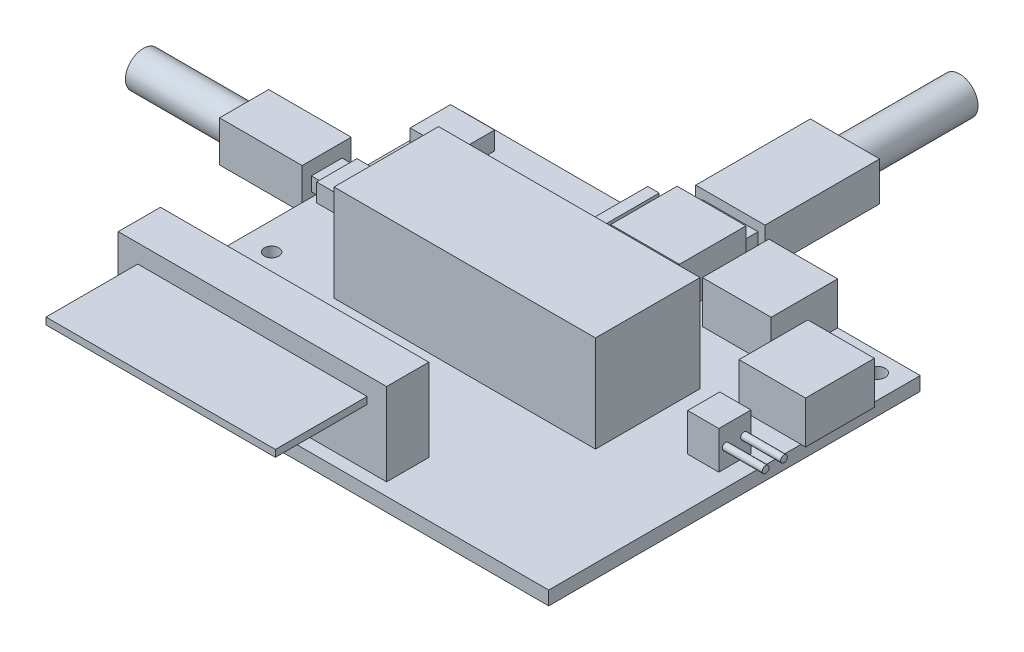
SolidWorks part; units mm, degrees
ref_plane "Front Plane" through (0, 0, 0) normal (0, 0, 1) x (1, 0, 0)
ref_plane "Top Plane" through (0, 0, 0) normal (0, 1, 0) x (1, 0, 0)
ref_plane "Right Plane" through (0, 0, 0) normal (1, 0, 0) x (0, 0, -1)
sketch "Sketch1" plane through (0, 0, 0) normal (0, 1, 0) x (1, 0, 0)
  line L1 (-50, -40.5) -> (50, -40.5)
  line L2 (-50, -40.5) -> (-50, 40.5)
  line L3 (-50, 40.5) -> (50, 40.5)
  line L4 (50, -40.5) -> (50, 40.5)
  line L5 (-50, -40.5) -> (50, 40.5) construction
  line L6 (-50, 40.5) -> (50, -40.5) construction
  circle A0 centre (44.8, 36.3) radius 1.75
  circle A1 centre (3.8, 19.5) radius 1.75
  circle A2 centre (-44.025, -18.275) radius 1.575
  circle A3 centre (-44.025, -6.875) radius 1.575
  point P0 (0, 0)
  point P14 (0, 0)
  dimension "D3" = 5.2
  dimension "D4" = 4.2
  dimension "D5" = 3.5
  dimension "D8" = 3.5
  dimension "D9" = 4.4
  dimension "D10" = 8.25
  dimension "D11" = 3.15
  dimension "D12" = 20.65
  dimension "D1" = 100
  dimension "D2" = 81
  dimension "D6" = 21
  dimension "D7" = 46.2
extrude "Boss-Extrude1" add sketch "Sketch1" along normal blind 3
sketch "Sketch2" plane through (0, 3, 0) normal (0, 1, 0) x (1, 0, 0)
  line L0 (-50, 40.5) -> (-50, -40.5) construction
  line L1 (-46.59, -28.55) -> (11.91, -28.55)
  line L2 (-46.59, -28.55) -> (-46.59, -37.75)
  line L3 (-46.59, -37.75) -> (11.91, -37.75)
  line L4 (11.91, -28.55) -> (11.91, -37.75)
  line L5 (-50, -40.5) -> (50, -40.5) construction
  dimension "D1" = 3.41
  dimension "D2" = 58.5
  dimension "D3" = 2.75
  dimension "D4" = 9.2
extrude "Boss-Extrude2" add sketch "Sketch2" along normal blind 18
sketch "Sketch3" plane through (0, 0, 37.75) normal (0, 0, 1) x (1, 0, 0)
  line L0 (-46.59, 21) -> (11.91, 21) construction
  line L1 (-42.34, 17) -> (7.66, 17)
  line L2 (-42.34, 17) -> (-42.34, 15.5)
  line L3 (-42.34, 15.5) -> (7.66, 15.5)
  line L4 (7.66, 17) -> (7.66, 15.5)
  point P6 (-17.34, 21)
  point P7 (-17.34, 17)
  dimension "D1" = 50
  dimension "D2" = 1.5
  dimension "D3" = 4
extrude "Boss-Extrude3" add sketch "Sketch3" along normal blind 20
sketch "Sketch4" plane through (0, 3, 0) normal (0, 1, 0) x (1, 0, 0)
  line L0 (50, 40.5) -> (-50, 40.5) construction
  line L1 (36.5, 29.5) -> (51, 29.5)
  line L2 (36.5, 29.5) -> (36.5, 14.5)
  line L3 (36.5, 14.5) -> (51, 14.5)
  line L4 (51, 29.5) -> (51, 14.5)
  line L5 (-3, 40.5) -> (12, 40.5)
  line L6 (-3, 40.5) -> (-3, 26)
  line L7 (-3, 26) -> (12, 26)
  line L8 (12, 40.5) -> (12, 26)
  line L9 (17, 40.5) -> (32, 40.5)
  line L10 (17, 40.5) -> (17, 26)
  line L11 (17, 26) -> (32, 26)
  line L12 (32, 40.5) -> (32, 26)
  line L13 (50, -40.5) -> (50, 40.5) construction
  dimension "D1" = 15
  dimension "D2" = 11
  dimension "D3" = 15
  dimension "D4" = 15
  dimension "D5" = 14.5
  dimension "D6" = 1
  dimension "D7" = 5
  dimension "D8" = 18
extrude "Boss-Extrude4" add sketch "Sketch4" along normal blind 9.25
sketch "Sketch5" plane through (0, 3, 0) normal (0, 1, 0) x (1, 0, 0)
  line L0 (-3, 40.5) -> (-50, 40.5) construction
  line L1 (-6.9, 38) -> (-4.4, 38)
  line L2 (-6.9, 38) -> (-6.9, 14)
  line L3 (-6.9, 14) -> (-4.4, 14)
  line L4 (-4.4, 38) -> (-4.4, 14)
  line L5 (-50, 40.5) -> (-50, -40.5) construction
  dimension "D1" = 2.5
  dimension "D2" = 24
  dimension "D3" = 2.5
  dimension "D4" = 43.1
extrude "Boss-Extrude5" add sketch "Sketch5" along normal blind 8.5
ref_plane "Plane1" through (0, 6.125, 0) normal (0, 1, 0) x (1, 0, 0)
sketch "Sketch6" plane through (0, 6.125, 0) normal (0, 1, 0) x (1, 0, 0)
  line L0 (12, 40.5) -> (-3, 40.5) construction
  line L1 (-1.55, 40.5) -> (10.55, 40.5)
  line L2 (-1.55, 40.5) -> (-1.55, 44.6)
  line L3 (-1.55, 44.6) -> (10.55, 44.6)
  line L4 (10.55, 40.5) -> (10.55, 44.6)
  line L5 (-3, 26) -> (12, 26) construction
  line L6 (-3.05, 44.6) -> (12.05, 44.6)
  line L7 (-3.05, 44.6) -> (-3.05, 69.6)
  line L8 (-3.05, 69.6) -> (12.05, 69.6)
  line L9 (12.05, 44.6) -> (12.05, 69.6)
  point P12 (4.5, 26)
  point P13 (4.5, 40.5)
  point P14 (4.5, 69.6)
  dimension "D1" = 12.1
  dimension "D2" = 15.1
  dimension "D3" = 4.1
  dimension "D4" = 25
extrude "Boss-Extrude6" add sketch "Sketch6" along normal mid plane 4.5 contours L1 L4 L3 L2 region at (4.5, 6.125, -42.55)
extrude "Boss-Extrude7" add sketch "Sketch6<3>" along normal mid plane 8.5 contours L8 L9 L6 L7
sketch "Sketch6<3>" plane through (0, 6.125, 0) normal (0, 1, 0) x (1, 0, 0) same geometry as "Sketch6"
sketch "Sketch7" plane through (0, 0, -69.6) normal (0, 0, -1) x (-1, 0, 0)
  line L0 (3.05, 6.125) -> (-12.05, 6.125) construction
  circle A0 centre (-4.5, 6.125) radius 4
  dimension "D1" = 8
extrude "Boss-Extrude8" add sketch "Sketch7" along normal blind 25
sketch "Sketch8" plane through (0, 3, 0) normal (0, 1, 0) x (1, 0, 0)
  line L0 (-50, 40.5) -> (-50, -40.5) construction
  line L1 (-48.4, 36.5) -> (-38.8, 36.5)
  line L2 (-48.4, 36.5) -> (-48.4, 27.7)
  line L3 (-48.4, 27.7) -> (-38.8, 27.7)
  line L4 (-38.8, 36.5) -> (-38.8, 27.7)
  line L5 (-3, 40.5) -> (-50, 40.5) construction
  line L7 (-48.4, 16.1) -> (-38.8, 16.1)
  line L8 (-48.4, 16.1) -> (-48.4, 7.3)
  line L9 (-48.4, 7.3) -> (-38.8, 7.3)
  line L10 (-38.8, 16.1) -> (-38.8, 7.3)
  dimension "D1" = 8.8
  dimension "D2" = 9.6
  dimension "D3" = 1.6
  dimension "D4" = 4
  dimension "D5" = 11.6
extrude "Boss-Extrude9" add sketch "Sketch8" along normal blind 3.95
ref_plane "Plane2" through (0, 4.975, 0) normal (0, 1, 0) x (1, 0, 0)
sketch "Sketch9" plane through (0, 4.975, 0) normal (0, 1, 0) x (1, 0, 0)
  line L0 (-48.4, 16.1) -> (-48.4, 7.3) construction
  line L1 (-48.4, 8.34) -> (-50.6, 8.34)
  line L2 (-48.4, 8.34) -> (-48.4, 15.06)
  line L3 (-48.4, 15.06) -> (-50.6, 15.06)
  line L4 (-50.6, 8.34) -> (-50.6, 15.06)
  line L5 (-38.8, 7.3) -> (-38.8, 16.1) construction
  line L6 (-50.6, 6.35) -> (-68.6, 6.35)
  line L7 (-50.6, 6.35) -> (-50.6, 17.05)
  line L8 (-50.6, 17.05) -> (-68.6, 17.05)
  line L9 (-68.6, 6.35) -> (-68.6, 17.05)
  line L10 (-38.8, 7.3) -> (-38.8, 16.1) construction
  point P14 (-38.8, 11.7)
  point P15 (-48.4, 11.7)
  point P16 (-68.6, 11.7)
  dimension "D1" = 11.8
  dimension "D2" = 18
  dimension "D3" = 6.72
  dimension "D4" = 10.7
extrude "Boss-Extrude10" add sketch "Sketch9" along normal mid plane 3 contours L4 L1 L2 L3 region at (-49.5, 4.975, -11.7)
extrude "Boss-Extrude11" add sketch "Sketch9<3>" along normal mid plane 8.9 contours L6 L9 L8 L7
sketch "Sketch9<3>" plane through (0, 4.975, 0) normal (0, 1, 0) x (1, 0, 0) same geometry as "Sketch9"
sketch "Sketch10" plane through (-68.6, 0, 0) normal (-1, 0, 0) x (0, 0, 1)
  line L0 (-8.34, 4.975) -> (-15.06, 4.975) construction
  circle A0 centre (-11.7, 4.975) radius 3.875
  dimension "D1" = 7.75
extrude "Boss-Extrude12" add sketch "Sketch10" along normal blind 22
sketch "Sketch11" plane through (0, 3, 0) normal (0, 1, 0) x (1, 0, 0)
  line L0 (-6.9, 14) -> (-4.4, 14) construction
  line L1 (-28.5, 13.999) -> (28.5, 13.999)
  line L2 (-28.5, 13.999) -> (-28.5, -8.801)
  line L3 (-28.5, -8.801) -> (28.5, -8.801)
  line L4 (28.5, 13.999) -> (28.5, -8.801)
  line L5 (-50, 40.5) -> (-50, -40.5) construction
  dimension "D1" = 22.8
  dimension "D2" = 57
  dimension "D3" = 0.001
  dimension "D4" = 21.5
extrude "Boss-Extrude13" add sketch "Sketch11" along normal blind 21
sketch "Sketch12" plane through (0, 3, 0) normal (0, 1, 0) x (1, 0, 0)
  line L0 (36.5, 14.5) -> (50, 14.5) construction
  line L1 (39.5, 7.3) -> (46.3, 7.3)
  line L2 (39.5, 7.3) -> (39.5, 0.3)
  line L3 (39.5, 0.3) -> (46.3, 0.3)
  line L4 (46.3, 7.3) -> (46.3, 0.3)
  line L5 (50, -40.5) -> (50, 14.5) construction
  dimension "D1" = 7.2
  dimension "D2" = 7
  dimension "D3" = 6.8
  dimension "D4" = 10.5
extrude "Boss-Extrude14" add sketch "Sketch12" along normal blind 8.25
sketch "Sketch13" plane through (46.3, 0, 0) normal (1, 0, 0) x (0, 0, -1)
  line L0 (3.8, 11.25) -> (3.8, 3) construction
  line L1 (0.3, 11.25) -> (7.3, 11.25) construction
  line L2 (0.3, 3) -> (7.3, 3) construction
  circle A0 centre (1.8, 7.125) radius 0.75
  circle A1 centre (5.8, 7.125) radius 0.75
  point P14 (3.8, 7.125)
  dimension "D1" = 1.5
  dimension "D2" = 2
extrude "Boss-Extrude15" add sketch "Sketch13" along normal offset from surface (8.7 mm away) 5 up to face at (50, 2, -7.3333) offset beyond the face yes
